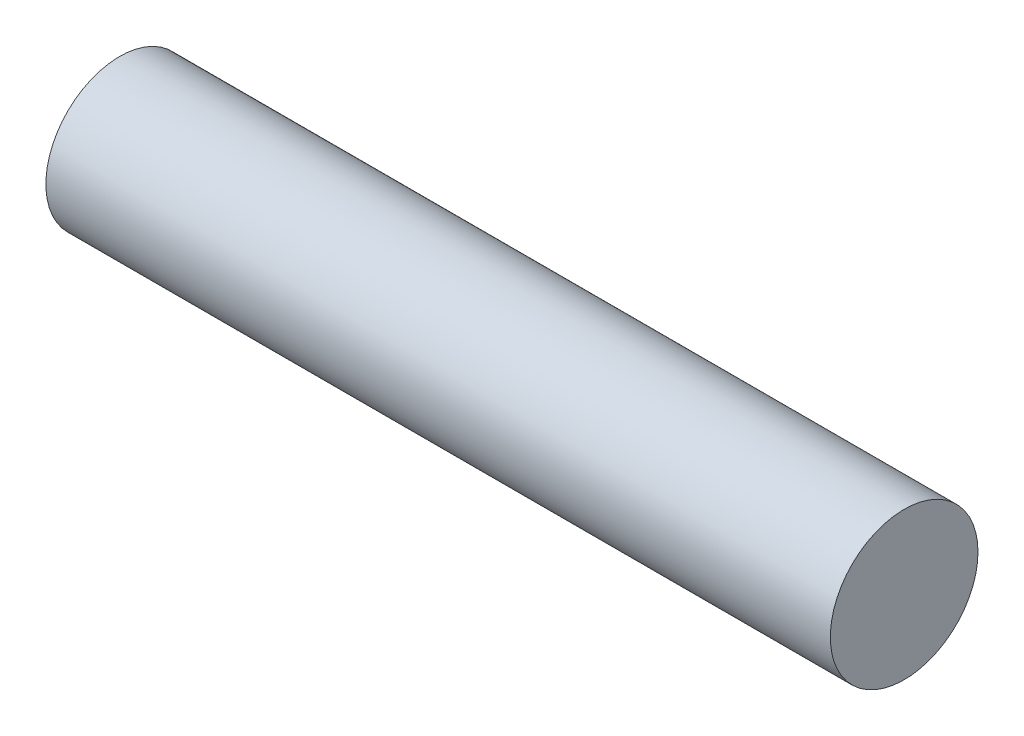
SolidWorks part; units mm, degrees
ref_plane "Front Plane" through (0, 0, 0) normal (0, 0, 1) x (1, 0, 0)
ref_plane "Top Plane" through (0, 0, 0) normal (0, 1, 0) x (1, 0, 0)
ref_plane "Right Plane" through (0, 0, 0) normal (1, 0, 0) x (0, 0, -1)
sketch "Sketch1" plane through (0, 0, 0) normal (1, 0, 0) x (0, 0, -1)
  circle A0 centre (0, 0) radius 80
extrude "FoamBody" add sketch "Sketch1" against normal blind 850 separate body
sketch "Sketch2" plane through (0, 0, 0) normal (0, 1, 0) x (1, 0, 0)
  line L1 (-343.5, -30) -> (-178.5, -30)
  line L2 (-343.5, -30) -> (-343.5, 30)
  line L3 (-343.5, 30) -> (-178.5, 30)
  line L4 (-178.5, -30) -> (-178.5, 30)
extrude "battery bay" cut sketch "Sketch2" against normal blind 60 from offset 10
sketch "Sketch3" plane through (0, 0, 0) normal (0, 1, 0) x (1, 0, 0)
  line L1 (-300, -40) -> (-150, -40)
  line L2 (-300, -40) -> (-300, 40)
  line L3 (-300, 40) -> (-150, 40)
  line L4 (-150, -40) -> (-150, 40)
extrude "Foam" cut sketch "Sketch3" along normal blind 35 from offset 10
sketch "Sketch4" plane through (0, 0, 0) normal (0, 1, 0) x (1, 0, 0)
  line L1 (-338.5, -24) -> (-183.5, -24)
  line L2 (-338.5, -24) -> (-338.5, 24)
  line L3 (-338.5, 24) -> (-183.5, 24)
  line L4 (-183.5, -24) -> (-183.5, 24)
extrude "Battery" add sketch "Sketch4" along normal blind 3 and the other way blind 47 separate body
sketch "Sketch5" plane through (0, 0, 0) normal (0, 1, 0) x (1, 0, 0)
  line L1 (-251, -16) -> (-199, -16)
  line L2 (-251, -16) -> (-251, 16)
  line L3 (-251, 16) -> (-199, 16)
  line L4 (-199, -16) -> (-199, 16)
extrude "FC" add sketch "Sketch5" along normal blind 17 from offset 13 separate body
